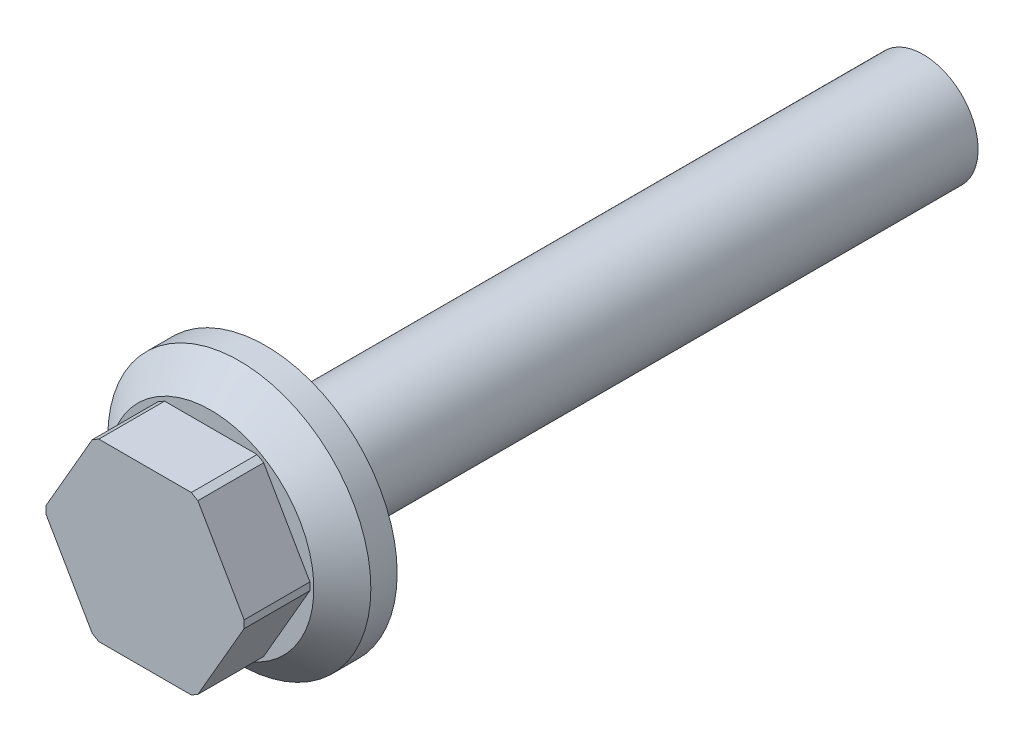
SolidWorks part; units mm, degrees
material "AISI 1020 Steel, Cold Rolled"
ref_plane "Płaszczyzna przednia" through (0, 0, 0) normal (0, 0, 1) x (1, 0, 0)
ref_plane "Płaszczyzna górna" through (0, 0, 0) normal (0, 1, 0) x (1, 0, 0)
ref_plane "Płaszczyzna prawa" through (0, 0, 0) normal (1, 0, 0) x (0, 0, -1)
sketch "Sketch1" plane through (0, 0, 0) normal (0, 1, 0) x (1, 0, 0)
  line L0 (0, 0) -> (2.5, 0)
  line L1 (2.5, 0) -> (2.5, 30)
  line L2 (2.5, 30) -> (0, 30)
  line L3 (0, 30) -> (0, 0)
  dimension "D1" = 30
  dimension "D2" = 2.5
revolve "Revolve1" add sketch "Sketch1" angle 360 about L3
sketch "Sketch2" plane through (0, 0, 0) normal (0, 0, 1) x (1, 0, 0)
  circle A0 centre (0, 0) radius 6
  dimension "D1" = 12
extrude "Boss-Extrude1" add sketch "Sketch2" along normal blind 1
sketch "Sketch3" plane through (0, 0, 1) normal (0, 0, 1) x (1, 0, 0)
  line L1 (-3.8945, 2.4832) -> (-4.0978, -2.1311) construction
  line L2 (-4.0978, -2.1311) -> (-0.2033, -4.6143) construction
  line L3 (-0.2033, -4.6143) -> (3.8945, -2.4832) construction
  line L4 (3.8945, -2.4832) -> (4.0978, 2.1311) construction
  line L5 (4.0978, 2.1311) -> (0.2033, 4.6143) construction
  line L6 (0.2033, 4.6143) -> (-3.8945, 2.4832) construction
  circle A0 centre (0, 0) radius 4 construction
  circle A1 centre (0, 0) radius 4.4
  dimension "D2" = 8.8
  dimension "D1" = 8
extrude "Boss-Extrude2" add sketch "Sketch3" along normal blind 1.5
chamfer "Chamfer1" distance 1.8 angle 45 1 edges at (4.4, 0, 1)
sketch "Sketch4" plane through (0, 0, 2.5) normal (0, 0, 1) x (1, 0, 0)
  line L1 (-2.3094, 4) -> (-4.6188, 0)
  line L2 (-4.6188, 0) -> (-2.3094, -4)
  line L3 (-2.3094, -4) -> (2.3094, -4)
  line L4 (2.3094, -4) -> (4.6188, 0)
  line L5 (4.6188, 0) -> (2.3094, 4)
  line L6 (2.3094, 4) -> (-2.3094, 4)
  circle A0 centre (0, 0) radius 4 construction
  dimension "D1" = 8
extrude "Boss-Extrude3" add sketch "Sketch4" along normal blind 3 and the other way blind 1.5
chamfer "Chamfer2" distance 0.2 angle 30 6 edges at (4.6188, 0, 4) (-4.6188, 0, 4) (-2.3094, -4, 4) (2.3094, -4, 4) (2.3094, 4, 4) (-2.3094, 4, 4) first distance on face at (3.4641, -2, 4) first distance on face at (-3.4641, -2, 4) first distance on face at (0, 4, 4)
